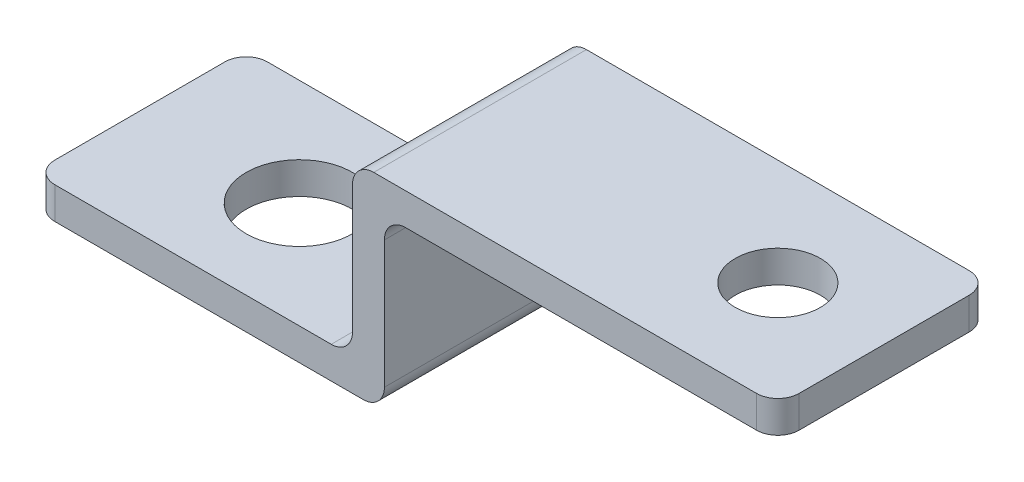
SolidWorks part; units mm, degrees
ref_plane "Ön Düzlem" through (0, 0, 0) normal (0, 0, 1) x (1, 0, 0)
ref_plane "Üst Düzlem" through (0, 0, 0) normal (0, 1, 0) x (1, 0, 0)
ref_plane "Sağ Düzlem" through (0, 0, 0) normal (1, 0, 0) x (0, 0, -1)
sketch "Sketch1" plane through (0, 0, 0) normal (0, 0, 1) x (1, 0, 0)
  line L0 (0, 0) -> (15, 0)
  line L1 (15, 0) -> (15, 8)
  line L2 (15, 8) -> (35, 8)
extrude "Extrude-Thin1" add sketch "Sketch1" along normal blind 10 thin thin type one direction wall 1.5
sketch "Sketch2" plane through (0, 8, 0) normal (0, 1, 0) x (1, 0, 0)
  line L0 (0, -10) -> (0, 0) construction
  line L1 (35, -10) -> (35, 0) construction
  line L2 (0, 0) -> (15, 0) construction
  line L3 (15, -10) -> (35, -10) construction
  circle A0 centre (30, -5) radius 2
  circle A1 centre (7.5, -5) radius 2.5
  point P6 (0, -5)
  dimension "D1" = 7.5
  dimension "D2" = 5
  dimension "D3" = 5
  dimension "D4" = 5
extrude "Cut-Extrude1" cut sketch "Sketch2" against normal through all
fillet "Fillet2" radius 1 8 edges at (15, 0, 5) (16.5, 6.5, 5) (15, 8, 5) (16.5, -1.5, 5) (35, 7.25, 10) (35, 7.25, 0) (0, -0.75, 10) (0, -0.75, 0)
